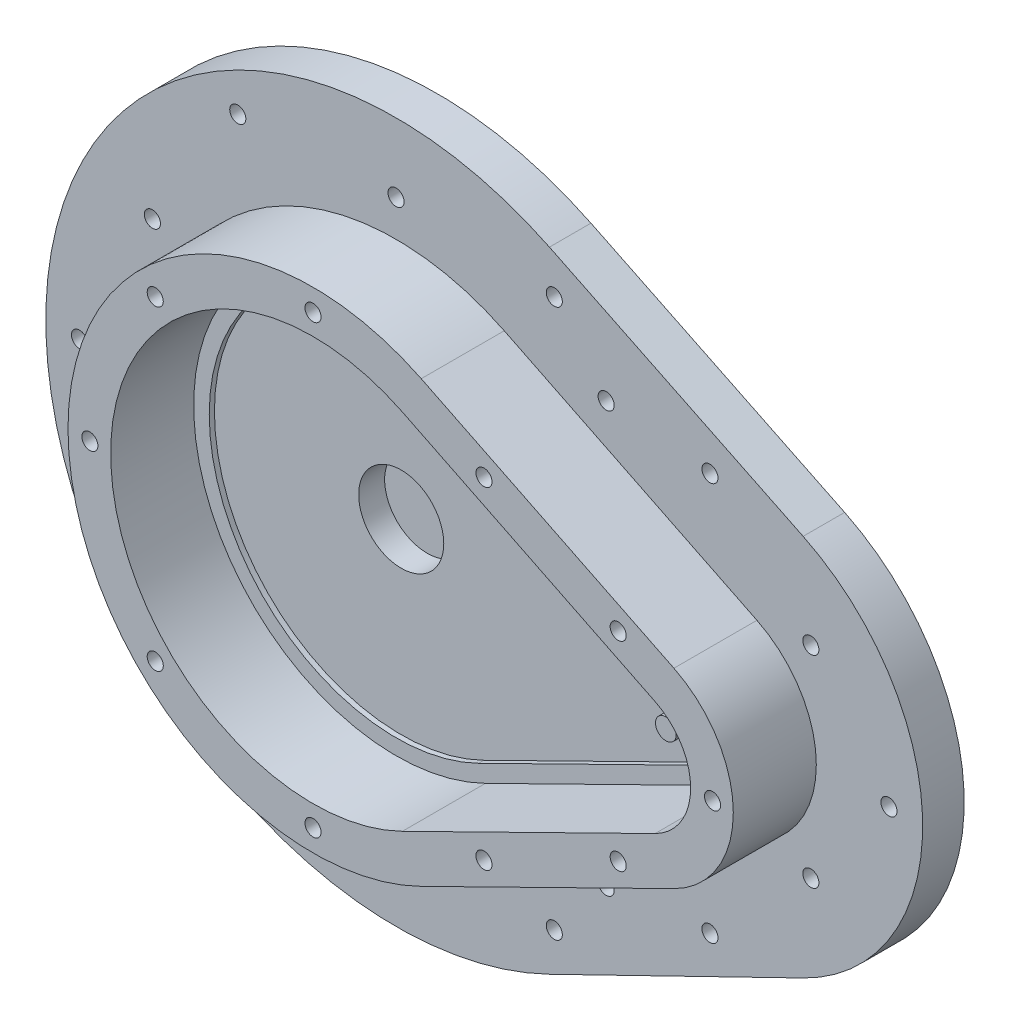
SolidWorks part; units mm, degrees
ref_plane "Front Plane" through (0, 0, 0) normal (0, 0, 1) x (1, 0, 0)
ref_plane "Top Plane" through (0, 0, 0) normal (0, 1, 0) x (1, 0, 0)
ref_plane "Right Plane" through (0, 0, 0) normal (1, 0, 0) x (0, 0, -1)
sketch "Sketch1" plane through (0, 0, 0) normal (0, 0, 1) x (1, 0, 0)
  line L0 (29.5661, 60.6803) -> (78.4587, 36.8576)
  line L1 (0, 0) -> (60.5, 0) construction
  line L3 (29.5661, -60.6803) -> (78.4587, -36.8576)
  circle A1 centre (0, 0) radius 67.5 construction
  circle A11 centre (60.5, 0) radius 41 construction
  arc A12 (29.5661, 60.6803) -> (29.5661, -60.6803) centre (0, 0) ccw
  arc A13 (78.4587, 36.8576) -> (78.4587, -36.8576) centre (60.5, 0) cw
  point P22 (0, 0)
extrude "Boss-Extrude2" add sketch "Sketch1" along normal blind 8
sketch "Sketch5" plane through (0, 0, 8) normal (0, 0, 1) x (1, 0, 0)
  line L0 (20.8559, 42.3656) -> (69.5542, 18.3922)
  line L1 (69.5542, -18.3922) -> (20.8559, -42.3656)
  line L2 (17.225, 34.99) -> (65.9233, 11.0166)
  line L3 (17.225, -34.99) -> (65.9233, -11.0166)
  line L4 (0, 0) -> (60.5, 0) construction
  circle A0 centre (0, 0) radius 43 construction
  circle A1 centre (60.5, 0) radius 16.5 construction
  circle A4 centre (60.5, 0) radius 12.2792 construction
  circle A5 centre (60.5, 0) radius 20.5 construction
  circle A6 centre (0, 0) radius 39 construction
  circle A7 centre (0, 0) radius 47.2208 construction
  arc A8 (20.8559, 42.3656) -> (20.8559, -42.3656) centre (0, 0) ccw
  arc A9 (17.225, 34.99) -> (17.225, -34.99) centre (0, 0) ccw
  arc A10 (65.9233, 11.0166) -> (65.9233, -11.0166) centre (60.5, 0) cw
  arc A11 (69.5542, 18.3922) -> (69.5542, -18.3922) centre (60.5, 0) cw
extrude "Boss-Extrude3" add sketch "Sketch5" along normal blind 16
sketch "Sketch6" plane through (0, 0, 24) normal (0, 0, 1) x (1, 0, 0)
  line L0 (0, 0) -> (0, 43) construction
  line L1 (60.5, 0) -> (77, 0) construction
  line L2 (20.8559, 42.3656) -> (69.5542, 18.3922) construction
  line L3 (20.8559, -42.3656) -> (69.5542, -18.3922) construction
  line L4 (20.8559, 42.3656) -> (34.716, 35.5424) construction
  line L5 (34.716, 35.5424) -> (32.9494, 31.9537) construction
  line L6 (69.5542, 18.3922) -> (60.5824, 22.8088) construction
  line L7 (60.5824, 22.8088) -> (58.8157, 19.2201) construction
  line L8 (20.8559, -42.3656) -> (34.716, -35.5424) construction
  line L9 (34.716, -35.5424) -> (32.9494, -31.9537) construction
  line L10 (69.5542, -18.3922) -> (60.5824, -22.8088) construction
  line L11 (60.5824, -22.8088) -> (58.8157, -19.2201) construction
  line L12 (0, 0) -> (60.5, 0) construction
  circle A0 centre (0, 43) radius 1.55
  circle A1 centre (60.5, 0) radius 16.5 construction
  circle A8 centre (77, 0) radius 1.55
  circle A9 centre (0, 0) radius 47.2208 construction
  circle A10 centre (60.5, 0) radius 20.5 construction
  arc A11 (69.5542, 18.3922) -> (69.5542, -18.3922) centre (60.5, 0) cw construction
  arc A12 (20.8559, 42.3656) -> (20.8559, -42.3656) centre (0, 0) ccw construction
  circle A13 centre (58.8157, 19.2201) radius 1.55
  circle A14 centre (32.9494, 31.9537) radius 1.55
  circle A15 centre (58.8157, -19.2201) radius 1.55
  circle A16 centre (32.9494, -31.9537) radius 1.55
  circle A17 centre (-30.4056, 30.4056) radius 1.55
  circle A18 centre (-43, 0) radius 1.55
  circle A19 centre (-30.4056, -30.4056) radius 1.55
  circle A20 centre (0, -43) radius 1.55
  point P21 (0.2659, 0.1121)
  point P41 (0, 0)
  dimension "D1" = 5
extrude "Cut-Extrude1" cut sketch "Sketch6" against normal up to surface (24 mm away) up to face at (35.5062, 0, 0)
sketch "Sketch11" plane through (0, 0, 8) normal (0, 0, 1) x (1, 0, 0)
  line L0 (0, 0) -> (60.5, 0) construction
  line L1 (23.9475, 48.6458) -> (72.6458, 24.6724) construction
  line L2 (23.9475, -48.6458) -> (72.6458, -24.6724) construction
  line L4 (0, 0) -> (40.4982, 40.4982) construction
  line L5 (60.5, 0) -> (79.9454, 19.4454) construction
  line L6 (26.719, 54.837) -> (75.6116, 31.0144) construction
  line L7 (26.719, -54.837) -> (75.6116, -31.0144) construction
  line L8 (0, 0) -> (30.5, 52.8275) construction
  line L9 (60.5, -38.3774) -> (60.5, 38.3774) construction
  circle A15 centre (60.5, 0) radius 27.5 construction
  circle A16 centre (0, 0) radius 54.2208 construction
  circle A17 centre (0, 54.2208) radius 1.55
  circle A18 centre (-46.9566, 27.1104) radius 1.55
  circle A19 centre (-46.9566, -27.1104) radius 1.55
  circle A20 centre (0, -54.2208) radius 1.55
  circle A21 centre (79.9454, 19.4454) radius 1.55
  circle A22 centre (0, 0) radius 61 construction
  circle A23 centre (40.4982, 40.4982) radius 1.55
  circle A24 centre (79.9454, -19.4454) radius 1.55
  circle A25 centre (40.4982, -40.4982) radius 1.55
  circle A26 centre (60.5, 0) radius 34.5 construction
  circle A27 centre (30.5, 52.8275) radius 1.55
  circle A28 centre (-30.5, 52.8275) radius 1.55
  circle A29 centre (-61, 0) radius 1.55
  circle A30 centre (-30.5, -52.8275) radius 1.55
  circle A31 centre (30.5, -52.8275) radius 1.55
  circle A32 centre (60.5, 38.3774) radius 1.55
  circle A33 centre (60.5, -38.3774) radius 1.55
  circle A34 centre (95, 0) radius 1.55
  point P22 (0, 0)
  point P45 (0, 0)
  point P47 (60.5, 0)
extrude "Cut-Extrude4" cut sketch "Sketch11" along normal offset from surface 10 and the other way through all up to face at (1.55, 43, 0)
sketch "Sketch9" plane through (0, 0, 0) normal (0, 0, -1) x (-1, 0, 0)
  line L0 (-77, 0) -> (0, 0) construction
  circle A10 centre (-77, 0) radius 3.5
  circle A11 centre (-58.8157, 19.2201) radius 3.5
  circle A12 centre (-32.9494, 31.9537) radius 3.5
  circle A13 centre (0, 43) radius 3.5
  circle A14 centre (30.4056, 30.4056) radius 3.5
  circle A15 centre (30.4056, -30.4056) radius 3.5
  circle A16 centre (0, -43) radius 3.5
  circle A17 centre (-32.9494, -31.9537) radius 3.5
  circle A18 centre (-58.8157, -19.2201) radius 3.5
  circle A19 centre (43, 0) radius 3.5
  circle A20 centre (0, 54.2208) radius 3.5
  circle A21 centre (46.9566, 27.1104) radius 3.5
  circle A22 centre (46.9566, -27.1104) radius 3.5
  circle A23 centre (0, -54.2208) radius 3.5
  circle A24 centre (-40.4982, 40.4982) radius 3.5
  circle A25 centre (-79.9454, 19.4454) radius 3.5
  circle A26 centre (-40.4982, -40.4982) radius 3.5
  circle A27 centre (-79.9454, -19.4454) radius 3.5
  point P40 (0, 0)
extrude "Cut-Extrude3" cut sketch "Sketch9" against normal blind 3
sketch "Sketch12" plane through (0, 0, 8) normal (0, 0, 1) x (1, 0, 0)
  line L0 (15.9, 32.2985) -> (64.5983, 8.3251)
  line L1 (15.9, -32.2985) -> (64.5983, -8.3251)
  circle A0 centre (0, 0) radius 36 construction
  circle A1 centre (60.5, 0) radius 9.2792 construction
  arc A2 (15.9, 32.2985) -> (15.9, -32.2985) centre (0, 0) ccw
  arc A3 (64.5983, 8.3251) -> (64.5983, -8.3251) centre (60.5, 0) cw
extrude "Cut-Extrude6" cut sketch "Sketch12" against normal blind 1
sketch "Sketch8" plane through (0, 0, 7) normal (0, 0, 1) x (1, 0, 0)
  circle A0 centre (60.5, 0) radius 2
sketch "Sketch7" plane through (0, 0, 7) normal (0, 0, 1) x (1, 0, 0)
  circle A0 centre (0, 0) radius 8.2
extrude "Boss-Extrude4" add sketch "Sketch8" along normal blind 9.5
extrude "Cut-Extrude7" cut sketch "Sketch7" against normal blind 5
